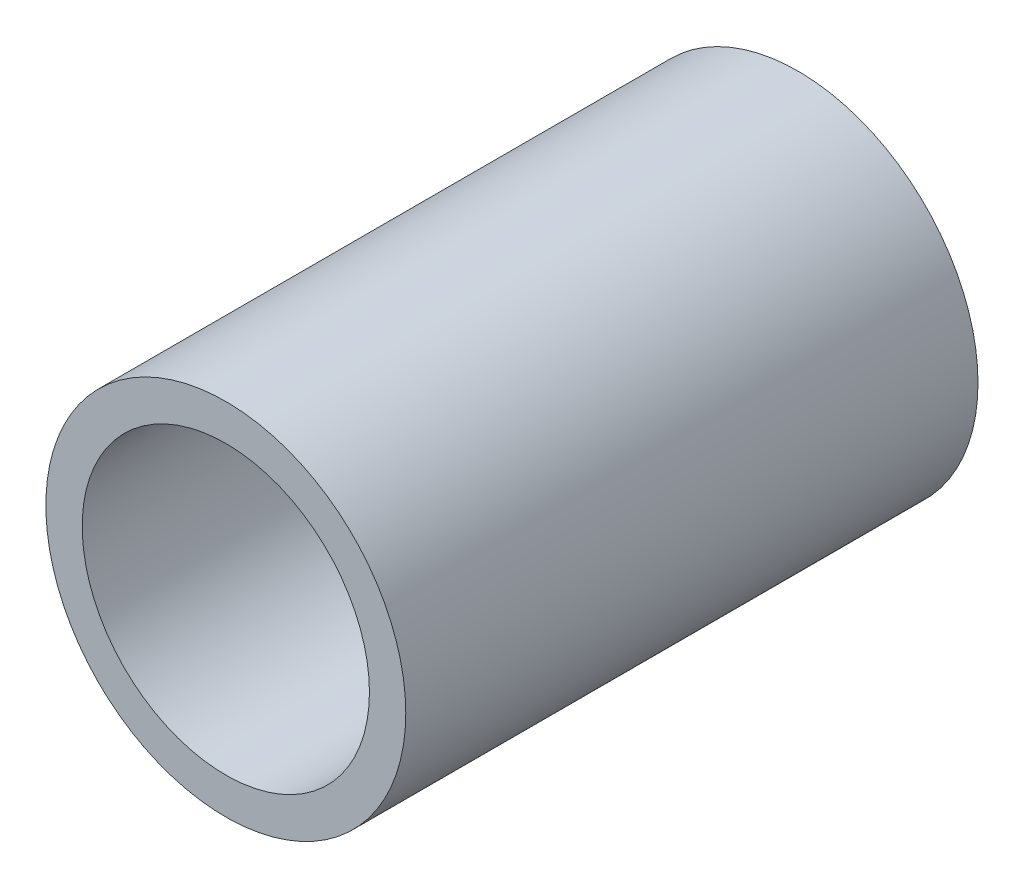
SolidWorks part; units mm, degrees
material "Tin Bearing Bronze"
ref_plane "Front Plane" through (0, 0, 0) normal (0, 0, 1) x (1, 0, 0)
ref_plane "Top Plane" through (0, 0, 0) normal (0, 1, 0) x (1, 0, 0)
ref_plane "Right Plane" through (0, 0, 0) normal (1, 0, 0) x (0, 0, -1)
sketch "Sketch1" plane through (0, 0, 0) normal (0, 0, 1) x (1, 0, 0)
  circle A0 centre (0, 0) radius 3.9942
  circle A1 centre (0, 0) radius 3.1877
  dimension "OD" = 7.9883
  dimension "ID" = 6.3754
sketch "Sketch2" plane through (0, 0, 0) normal (1, 0, 0) x (0, 0, -1)
  line L2 (6.35, 0) -> (-6.35, 0) construction
  line L4 (-6.35, -3.9942) -> (-6.35, 3.9941) construction
  line L5 (-6.35, -3.1877) -> (6.35, -3.1877)
  line L6 (6.35, 3.1877) -> (-6.35, 3.1877)
  line L7 (6.35, -3.9941) -> (6.35, 3.9941) construction
  line L8 (-6.35, 3.9941) -> (6.35, 3.9941) construction
  line L9 (-6.35, -3.9942) -> (6.35, -3.9941) construction
  line L10 (0, 3.9942) -> (0, -3.9942) construction
  line L11 (0, 3.1877) -> (0, -3.1877) construction
  point P4 (0, -3.1877)
  point P7 (0, 3.1877)
  point P8 (0, 0)
  point P12 (-6.35, 0)
  point P15 (6.35, 0)
  point P16 (0, -3.9942)
  point P17 (0, 3.9942)
  dimension "Length" = 12.7
sketch "Sketch5" plane through (0, 0, 0) normal (0, 0, 1) x (1, 0, 0)
  circle A1 centre (0, 0) radius 3.1877
  circle A2 centre (0, 0) radius 3.1877
  circle A3 centre (0, 0) radius 3.9942
  circle A4 centre (0, 0) radius 3.9942
  dimension "D1" = 0
  dimension "D2" = 0
extrude "Boss-Extrude1" add sketch "Sketch5" along normal up to vertex (6.35 mm away) and the other way up to vertex (6.35 mm away) up to point (0, 0, 6.35) other way up to point (0, 0, -6.35)
sketch "Sketch4" plane through (0, 0, 6.35) normal (0, 0, 1) x (1, 0, 0)
  line L0 (0, 0) -> (-2.254, 2.254)
  line L2 (0, -3.9942) -> (0, 3.9941) construction
  circle A1 centre (0, 0) radius 3.1877 construction
  dimension "D1" = 45
equation "\"D1\"= \"Length@Sketch2\""
